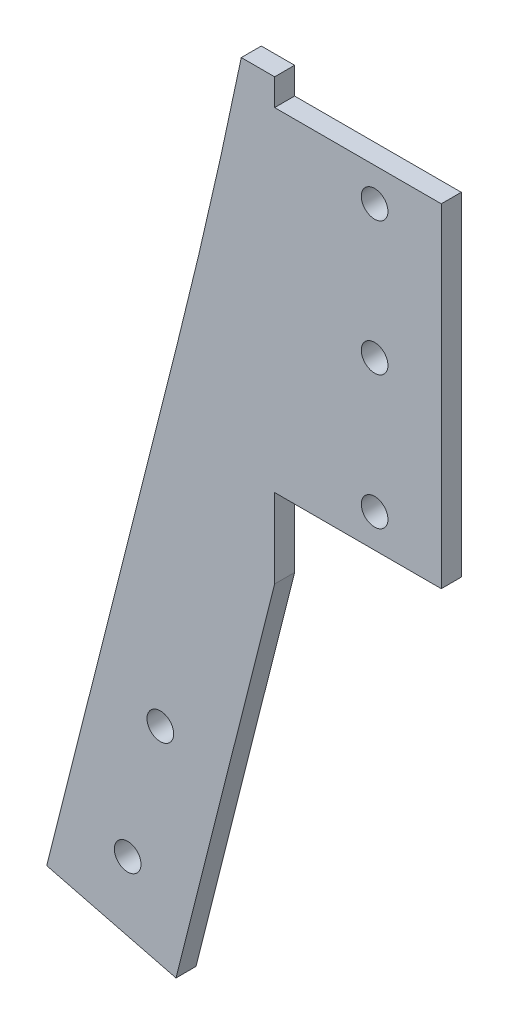
SolidWorks part; units mm, degrees
ref_plane "前视基准面" through (0, 0, 0) normal (0, 0, 1) x (1, 0, 0)
ref_plane "上视基准面" through (0, 0, 0) normal (0, 1, 0) x (1, 0, 0)
ref_plane "右视基准面" through (0, 0, 0) normal (1, 0, 0) x (0, 0, -1)
sketch "草图1" plane through (0, 0, 0) normal (0, 0, 1) x (1, 0, 0)
  line L0 (0, 0) -> (125, 0) construction
  line L1 (125, 0) -> (125, 495) construction
  line L2 (125, 495) -> (0, 0) construction
  line L3 (125, 470) -> (148, 470)
  line L4 (148, 470) -> (148, 520)
  line L5 (148, 520) -> (123, 520)
  line L6 (123, 520) -> (118, 520)
  line L7 (118, 520) -> (88.8152, 404.428)
  line L8 (88.8152, 404.428) -> (108.2064, 399.5312)
  line L12 (118, 498.4063) -> (118, 414.4174) construction
  line L13 (108.2064, 399.5312) -> (118, 438.3138)
  line L14 (118, 438.3138) -> (123, 458.1138)
  line L15 (125, 470) -> (124.1412, 470)
  line L16 (98.5108, 401.9796) -> (108.3044, 440.7622) construction
  line L17 (138, 475) -> (138, 495) construction
  line L18 (124.1412, 470) -> (123, 470)
  line L19 (118, 520) -> (123, 520)
  line L20 (118, 520) -> (118, 524)
  line L21 (118, 524) -> (123, 524)
  line L22 (123, 520) -> (123, 524)
  line L23 (123, 470) -> (123, 458.1138)
  circle A0 centre (100.9592, 411.6753) radius 2
  circle A1 centre (105.856, 431.0665) radius 2
  circle A2 centre (138, 475) radius 2
  circle A3 centre (138, 515) radius 2
  circle A4 centre (138, 495) radius 2
  point P4 (125, 470)
  dimension "D11" = 4
  dimension "D12" = 4
  dimension "D13" = 20
  dimension "D14" = 10
  dimension "D15" = 4
  dimension "D16" = 4
  dimension "D17" = 4
  dimension "D18" = 20
  dimension "D19" = 20
  dimension "D22" = 25
  dimension "D1" = 125
  dimension "D2" = 495
  dimension "D3" = 25
  dimension "D4" = 23
  dimension "D5" = 50
  dimension "D6" = 25
  dimension "D7" = 5
  dimension "D8" = 20
  dimension "D9" = 40
  dimension "D10" = 40
  dimension "D20" = 4
  dimension "D21" = 10
  dimension "D23" = 2
extrude "凸台-拉伸1" add sketch "草图1" along normal blind 3 contours L6 L22 L21 L20 | L15 L3 L4 L5 L6 L7 L8 L13 L14 A4 A3 A2 A1 A0 region at (119.7688, 468.5248, 0) region at (120.5, 522, 0)
fillet "圆角3" radius 1000 1 edges at (118, 520, 1.5)
